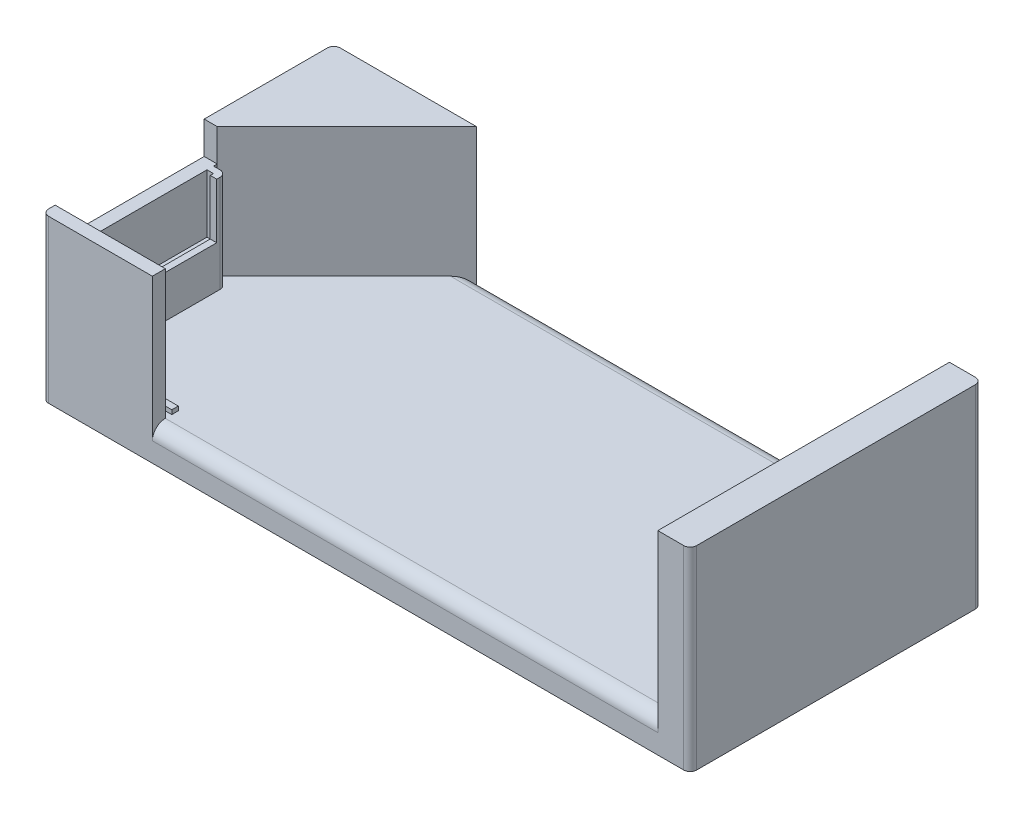
SolidWorks part; units mm, degrees
ref_plane "Front Plane" through (0, 0, 0) normal (0, 0, 1) x (1, 0, 0)
ref_plane "Top Plane" through (0, 0, 0) normal (0, 1, 0) x (1, 0, 0)
ref_plane "Right Plane" through (0, 0, 0) normal (1, 0, 0) x (0, 0, -1)
sketch "Sketch1" plane through (0, 0, 0) normal (0, 1, 0) x (1, 0, 0)
  line L0 (-48, -22.5) -> (-48, 2.5)
  line L1 (-50, -22.5) -> (50, -22.5)
  line L2 (-50, -22.5) -> (-50, 22.5)
  line L3 (-50, 22.5) -> (50, 22.5)
  line L4 (50, -22.5) -> (50, 22.5)
  line L5 (-50, -22.5) -> (50, 22.5) construction
  line L6 (-50, 22.5) -> (50, -22.5) construction
  line L7 (50, -22.5) -> (45, -22.5)
  line L8 (50, -22.5) -> (50, 22.5)
  line L9 (50, 22.5) -> (45, 22.5)
  line L10 (45, -22.5) -> (45, 22.5)
  line L11 (50, -22.5) -> (45, 22.5) construction
  line L12 (50, 22.5) -> (45, -22.5) construction
  line L13 (-48, 2.5) -> (-28, 22.5)
  line L14 (-48, -20.5) -> (-33, -20.5)
  line L15 (-33, -20.5) -> (-33, -22.5)
  line L16 (-33, 17.5) -> (-33, 22.5)
  line L17 (-48, -20.5) -> (-50, -20.5)
  line L18 (-48, 2.5) -> (-50, 2.5)
  line L20 (-48, -19.5) -> (-33, -19.5)
  line L21 (-48, -19.5) -> (-48, -18.5)
  line L22 (-48, -18.5) -> (-33, -18.5)
  line L23 (-33, -19.5) -> (-33, -18.5)
  line L24 (-48, -19.5) -> (-33, -18.5) construction
  line L25 (-48, -18.5) -> (-33, -19.5) construction
  point P0 (0, 0)
  point P8 (47.5, 0)
  point P23 (-40.5, -19)
  dimension "D1" = 100
  dimension "D2" = 45
  dimension "D3" = 5
  dimension "D4" = 135
  dimension "D5" = 2
  dimension "D6" = 15
  dimension "10" = 20
  dimension "D7" = 15
  dimension "D8" = 2
  dimension "D9" = 1
  dimension "D10" = 1
extrude "Boss-Extrude1" add sketch "Sketch1" against normal blind 5 contours L18 L13 L16 L3 L2 | L14 L15 L1 L10 L3 L13 L0 | L16 L13 L3 | L10 L1 L4 L3 | L0 L18 L2 L17 | L15 L14 L0 L1 | L0 L17 L2 L1 | L20 L23 L22 L0 region at (-49, 0, 21.5) region at (-40.5, 0, 21.5) region at (-49, 0, 9) region at (0.9674, 0, 0.5677) region at (-40.5, 0, 19) region at (47.5, 0, 0) region at (-43.2308, 0, -14.9725) region at (-31.3333, 0, -20.8333)
extrude "Boss-Extrude2" add sketch "Sketch1<4>" along normal blind 25 contours L10 L1 L4 L3 region at (47.5, 0, 0)
sketch "Sketch1<4>" plane through (0, 0, 0) normal (0, 1, 0) x (1, 0, 0) same geometry as "Sketch1"
extrude "Boss-Extrude3" add sketch "Sketch1<5>" along normal blind 20 contours L15 L14 L0 L1 | L0 L17 L2 L1 region at (-49, 0, 21.5) region at (-40.5, 0, 21.5)
sketch "Sketch1<5>" plane through (0, 0, 0) normal (0, 1, 0) x (1, 0, 0) same geometry as "Sketch1"
extrude "Boss-Extrude4" add sketch "Sketch1<6>" along normal blind 20 contours L18 L13 L16 L3 L2 | L16 L13 L3 region at (-43.2308, 0, -14.9725) region at (-31.3333, 0, -20.8333)
sketch "Sketch1<6>" plane through (0, 0, 0) normal (0, 1, 0) x (1, 0, 0) same geometry as "Sketch1"
extrude "Boss-Extrude5" add sketch "Sketch1<8>" along normal blind 15 contours L0 L18 L2 L17 region at (-49, 0, 9)
sketch "Sketch1<8>" plane through (0, 0, 0) normal (0, 1, 0) x (1, 0, 0) same geometry as "Sketch1"
extrude "Boss-Extrude6" add sketch "Sketch1<9>" along normal blind 0.65 from surface contours L20 L23 L22 L0 region at (-40.5, 0, 19) starting at face at (-14.2857, 0, 5.5)
sketch "Sketch1<9>" plane through (0, 0, 0) normal (0, 1, 0) x (1, 0, 0) same geometry as "Sketch1"
sketch "Sketch4" plane through (0, 0, 20.5) normal (0, 0, -1) x (-1, 0, 0)
  line L0 (33, 20) -> (33, 0) construction
  line L1 (42, 0) -> (43.5, 0)
  line L2 (42, 0) -> (42, 15)
  line L3 (42, 15) -> (43.5, 15)
  line L4 (43.5, 0) -> (43.5, 15)
  line L5 (42, 0) -> (43.5, 15) construction
  line L6 (42, 15) -> (43.5, 0) construction
  line L7 (50, 0) -> (-50, 0) construction
  line L9 (42, 15) -> (41.5, 15)
  line L10 (42, 15) -> (42, 0)
  line L11 (42, 0) -> (41.5, 0)
  line L12 (41.5, 15) -> (41.5, 0)
  line L13 (42, 15) -> (41.5, 0) construction
  line L14 (42, 0) -> (41.5, 15) construction
  point P4 (42.75, 7.5)
  point P9 (42.75, 15)
  point P12 (41.75, 7.5)
  line M5 (33, 0) -> (48, 0)
  dimension "D1" = 9
  dimension "D2" = 1.5
  dimension "D3" = 15
  dimension "D4" = 0.5
extrude "Boss-Extrude7" add sketch "Sketch4" along normal blind 1 contours L4 L3 L2 M5 region at (-42.75, 7.5, 20.5)
extrude "Boss-Extrude8" add sketch "Sketch4<4>" along normal blind 1 from surface contours L9 L12 L2 M5 | L4 L3 L2 M5 region at (-42.75, 7.5, 20.5) region at (-41.75, 7.5, 20.5) starting at face at (-42.75, 7.825, 19.5)
sketch "Sketch4<4>" plane through (0, 0, 20.5) normal (0, 0, -1) x (-1, 0, 0) same geometry as "Sketch4"
sketch "Sketch5" plane through (-48, 0, 0) normal (1, 0, 0) x (0, 0, -1)
  line L0 (-20.5, 15) -> (2.5, 15) construction
  line L1 (-17.3162, 15) -> (0.9338, 15)
  line L2 (-17.3162, 15) -> (-17.3162, 6)
  line L3 (-17.3162, 6) -> (0.9338, 6)
  line L4 (0.9338, 15) -> (0.9338, 6)
  line L5 (-17.3162, 15) -> (0.9338, 6) construction
  line L6 (-17.3162, 6) -> (0.9338, 15) construction
  line L7 (-18.5, 0) -> (2.5, 0) construction
  line L8 (-17.3162, 15) -> (-18.3162, 15)
  line L9 (-17.3162, 15) -> (-17.3162, 6)
  line L10 (-17.3162, 6) -> (-18.3162, 6)
  line L11 (-18.3162, 15) -> (-18.3162, 6)
  line L12 (-17.3162, 15) -> (-18.3162, 6) construction
  line L13 (-17.3162, 6) -> (-18.3162, 15) construction
  line L14 (-18.3162, 6) -> (1.9338, 6)
  line L15 (-18.3162, 6) -> (-18.3162, 0)
  line L16 (-18.3162, 0) -> (1.9338, 0)
  line L17 (1.9338, 6) -> (1.9338, 0)
  line L18 (-18.3162, 6) -> (1.9338, 0) construction
  line L19 (-18.3162, 0) -> (1.9338, 6) construction
  line L20 (1.9338, 6) -> (0.9338, 6)
  line L21 (1.9338, 6) -> (1.9338, 15)
  line L22 (1.9338, 15) -> (0.9338, 15)
  line L23 (0.9338, 6) -> (0.9338, 15)
  line L24 (1.9338, 6) -> (0.9338, 15) construction
  line L25 (1.9338, 15) -> (0.9338, 6) construction
  line L27 (-17.3162, 6) -> (-16.8162, 6)
  line L28 (-17.3162, 6) -> (-17.3162, 15)
  line L29 (-17.3162, 15) -> (-16.8162, 15)
  line L30 (-16.8162, 6) -> (-16.8162, 15)
  line L31 (-17.3162, 6) -> (-16.8162, 15) construction
  line L32 (-17.3162, 15) -> (-16.8162, 6) construction
  line L33 (0.4338, 6) -> (0.9338, 6)
  line L34 (0.4338, 6) -> (0.4338, 15)
  line L35 (0.4338, 15) -> (0.9338, 15)
  line L36 (0.9338, 6) -> (0.9338, 15)
  line L37 (0.4338, 6) -> (0.9338, 15) construction
  line L38 (0.4338, 15) -> (0.9338, 6) construction
  line L39 (-18.3162, 6) -> (0.9338, 6)
  line L40 (-18.3162, 6) -> (-18.3162, 6.5)
  line L41 (-18.3162, 6.5) -> (0.9338, 6.5)
  line L42 (0.9338, 6) -> (0.9338, 6.5)
  line L43 (-18.3162, 6) -> (0.9338, 6.5) construction
  line L44 (-18.3162, 6.5) -> (0.9338, 6) construction
  point P4 (-8.1912, 10.5)
  point P11 (-17.8162, 10.5)
  point P13 (-8.1912, 3)
  point P16 (1.4338, 10.5)
  point P20 (-17.0662, 10.5)
  point P24 (0.6838, 10.5)
  point P26 (-8.6912, 6.25)
  line M7 (-18.5, 0) -> (2.5, 0)
  line M9 (2.5, 15) -> (-20.5, 15)
  dimension "D1" = 9
  dimension "D2" = 18.25
  dimension "D3" = 1
  dimension "D4" = 1
  dimension "D5" = 0.5
  dimension "D6" = 0.5
  dimension "D7" = 0.5
extrude "Boss-Extrude9" add sketch "Sketch5" along normal blind 1 contours L17 L14 L3 L10 L15 M7 | L11 L41 L2 M9 | L41 L11 L10 L28 | L14 L21 L4 L36 M9 region at (-48, 10.75, 17.8162) region at (-48, 6.25, 17.8162) region at (-48, 3, 8.1912) region at (-48, 10.5, -1.4338)
extrude "Boss-Extrude11" add sketch "Sketch5<5>" along normal blind 1 from surface contours L11 L41 L2 M9 | L2 L41 L30 L1 | L41 L11 L10 L28 | L41 L28 L3 L30 | L17 L14 L3 L10 L15 M7 | L41 L30 L14 L34 | L34 L41 L4 M9 | L41 L34 L3 L36 | L14 L21 L4 L36 M9 region at (-48, 10.75, 17.0662) region at (-48, 10.75, 17.8162) region at (-48, 6.25, 17.0662) region at (-48, 6.25, 17.8162) region at (-48, 10.75, -0.6838) region at (-48, 6.25, 8.1912) region at (-48, 3, 8.1912) region at (-48, 10.5, -1.4338) region at (-48, 6.25, -0.6838) starting at face at (-47, 9, 8.1912)
sketch "Sketch5<5>" plane through (-48, 0, 0) normal (1, 0, 0) x (0, 0, -1) same geometry as "Sketch5"
fillet "Fillet1" radius 1 3 edges at (-46, 7.5, -1.9338) (-43.5, 7.825, 18.5) (-46, 7.5, 18.3162)
fillet "Fillet2" radius 1 4 edges at (50, 10, 22.5) (-50, 7.5, 22.5) (50, 10, -22.5) (-50, 7.5, -22.5)
fillet "Fillet3" radius 2 2 edges at (6, 0, 22.5) (8.5, 0, -22.5)
